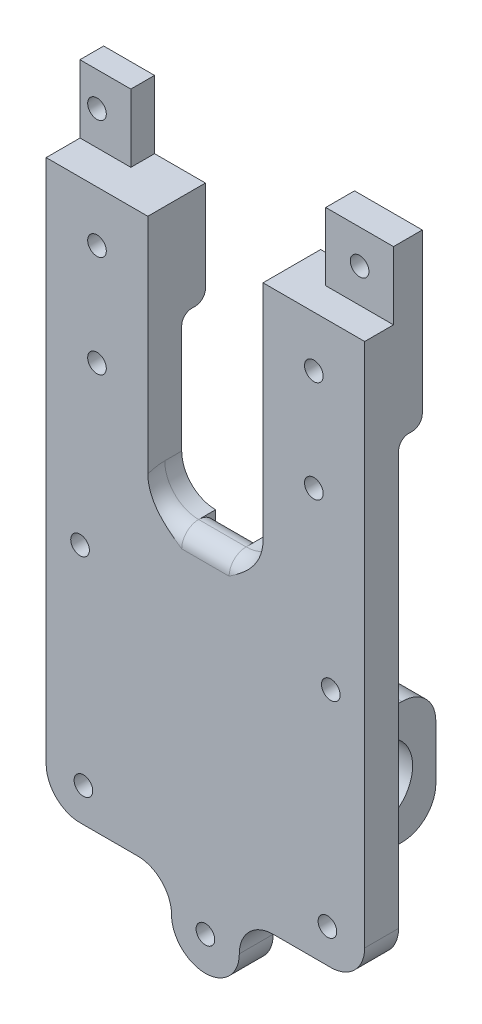
SolidWorks part; units mm, degrees
ref_plane "Front Plane" through (0, 0, 0) normal (0, 0, 1) x (1, 0, 0)
ref_plane "Top Plane" through (0, 0, 0) normal (0, 1, 0) x (1, 0, 0)
ref_plane "Right Plane" through (0, 0, 0) normal (1, 0, 0) x (0, 0, -1)
sketch "Sketch2" plane through (0, 0, -10) normal (0, 0, -1) x (-1, 0, 0)
  line L1 (-20, -75) -> (10, -75)
  line L2 (-20, -75) -> (-20, -205)
  line L3 (-20, -205) -> (10, -205)
  line L4 (10, -75) -> (10, -205)
  line L5 (44, -75) -> (74, -75)
  line L6 (44, -75) -> (44, -205)
  line L7 (44, -205) -> (74, -205)
  line L8 (74, -75) -> (74, -205)
  dimension "D1" = 130
  dimension "D2" = 130
  dimension "D3" = 30
  dimension "D4" = 30
extrude "Boss-Extrude1" add sketch "Sketch2" against normal up to surface (10 mm away)
sketch "Sketch3" plane through (0, 0, -10) normal (0, 0, -1) x (-1, 0, 0)
  line L0 (74, -205) -> (74, -75) construction
  line L1 (-20, -205) -> (74, -205)
  line L2 (-20, -205) -> (-20, -175)
  line L3 (-20, -175) -> (74, -175)
  line L4 (74, -205) -> (74, -175)
  dimension "D1" = 30
extrude "Boss-Extrude2" add sketch "Sketch3" against normal up to surface (10 mm away) up to face at (5, -140, 0)
fillet "Fillet1" radius 10 4 edges at (-74, -205, -5) (20, -205, -5) (-10, -175, -5) (-44, -175, -5)
sketch "Sketch4" plane through (0, 0, -10) normal (0, 0, -1) x (-1, 0, 0)
  line L0 (-20, -75) -> (-20, -155)
  line L1 (-20, -75) -> (-20, -195) construction
  line L2 (-20, -155) -> (74, -155)
  line L3 (74, -195) -> (74, -75) construction
  line L12 (-10, -205) -> (64, -205)
  line L13 (74, -195) -> (74, -75)
  line L14 (74, -75) -> (44, -75)
  line L15 (44, -75) -> (44, -165)
  line L16 (34, -175) -> (20, -175)
  line L17 (10, -165) -> (10, -75)
  line L18 (10, -75) -> (-20, -75)
  line L19 (-20, -75) -> (-20, -195)
  line L20 (-10, -205) -> (64, -205)
  line L21 (74, -195) -> (74, -75)
  line L22 (74, -75) -> (44, -75)
  line L23 (44, -75) -> (44, -165)
  line L24 (34, -175) -> (20, -175)
  line L25 (10, -165) -> (10, -75)
  line L26 (10, -75) -> (-20, -75)
  line L27 (-20, -75) -> (-20, -195)
  arc A4 (64, -205) -> (74, -195) centre (64, -195) ccw
  arc A5 (34, -175) -> (44, -165) centre (34, -165) ccw
  arc A6 (10, -165) -> (20, -175) centre (20, -165) ccw
  arc A7 (-20, -195) -> (-10, -205) centre (-10, -195) ccw
  arc A8 (64, -205) -> (74, -195) centre (64, -195) ccw
  arc A9 (34, -175) -> (44, -165) centre (34, -165) ccw
  arc A10 (10, -165) -> (20, -175) centre (20, -165) ccw
  arc A11 (-20, -195) -> (-10, -205) centre (-10, -195) ccw
  line M14 (-10, -205) -> (64, -205)
  arc M15 (64, -205) -> (74, -195) centre (64, -195) ccw
  line M16 (74, -195) -> (74, -75)
  line M18 (44, -75) -> (44, -165)
  arc M19 (44, -165) -> (34, -175) centre (34, -165) cw
  line M20 (34, -175) -> (20, -175)
  arc M21 (20, -175) -> (10, -165) centre (20, -165) cw
  line M22 (10, -165) -> (10, -75)
  line M24 (-20, -75) -> (-20, -195)
  arc M25 (-20, -195) -> (-10, -205) centre (-10, -195) ccw
  dimension "D1" = 80
  dimension "D2" = 0
extrude "Cut-Extrude1" cut sketch "Sketch4" against normal through all contours L2 M24 M25 M14 M15 M16 M18 M19 M20 M21 M22 region at (-27, -182.217, -10)
sketch "Sketch5" plane through (0, 0, -10) normal (0, 0, -1) x (-1, 0, 0)
  line L0 (74, -155) -> (74, -185)
  line L1 (-20, -155) -> (74, -155)
  line L2 (-20, -155) -> (-20, -185)
  line L3 (-20, -185) -> (74, -185)
  dimension "D1" = 30
extrude "Boss-Extrude3" add sketch "Sketch5" against normal up to surface (10 mm away) up to face at (5, -115, 0)
sketch "Sketch7" plane through (0, 0, -10) normal (0, 0, -1) x (-1, 0, 0)
  line L0 (10, -155) -> (-20, -155)
  line L2 (-20, -75) -> (-20, -185) construction
  line L4 (-5, -155) -> (-5, -175)
  line L5 (-10, -155) -> (-10, -175)
  line L6 (0, -155) -> (0, -175)
  line L7 (-10, -175) -> (0, -175)
  line L8 (-10, -155) -> (0, -155)
  line L9 (27, -155) -> (27, -148.1349)
  line L10 (44, -155) -> (10, -155) construction
  line L11 (64, -155) -> (54, -155)
  line L12 (64, -175) -> (54, -175)
  line L13 (54, -155) -> (54, -175)
  line L14 (64, -155) -> (64, -175)
  line L15 (59, -155) -> (59, -175)
  dimension "D3" = 20
  dimension "D1" = 5
  dimension "D2" = 5
extrude "Boss-Extrude4" add sketch "Sketch7" along normal blind 15 contours L5 L7 L4 L0 | L4 L7 L6 L0 | L15 L11 L13 L12 | L11 L15 L12 L14 region at (2.5, -165, -10) region at (7.5, -165, -10) region at (-61.5, -165, -10) region at (-56.5, -165, -10)
sketch "Sketch11" plane through (0, 0, -25) normal (0, 0, -1) x (-1, 0, 0)
  line L4 (54, -175) -> (64, -175)
  line L5 (64, -175) -> (64, -155)
  line L6 (64, -155) -> (54, -155)
  line L7 (54, -155) -> (54, -175)
  line L8 (54, -175) -> (64, -175)
  line L9 (64, -175) -> (64, -155)
  line L10 (64, -155) -> (54, -155)
  line L11 (54, -155) -> (54, -175)
  line L12 (-10, -155) -> (-10, -175)
  line L13 (-10, -175) -> (0, -175)
  line L14 (0, -175) -> (0, -155)
  line L15 (0, -155) -> (-10, -155)
  line L16 (-10, -155) -> (-10, -175)
  line L17 (-10, -175) -> (0, -175)
  line L18 (0, -175) -> (0, -155)
  line L19 (0, -155) -> (-10, -155)
  dimension "D1" = 0
  dimension "D2" = 0
extrude "Boss-Extrude5" add sketch "Sketch11" along normal blind 10
sketch "Sketch12" plane through (0, -175, 0) normal (0, -1, 0) x (1, 0, 0)
  line L4 (10, -10) -> (0, -10)
  line L5 (0, -10) -> (0, -35)
  line L6 (0, -35) -> (10, -35)
  line L7 (10, -35) -> (10, -10)
  line L8 (10, -10) -> (0, -10)
  line L9 (0, -10) -> (0, -35)
  line L10 (0, -35) -> (10, -35)
  line L11 (10, -35) -> (10, -10)
  line L12 (-54, -10) -> (-64, -10)
  line L13 (-64, -10) -> (-64, -35)
  line L14 (-64, -35) -> (-54, -35)
  line L15 (-54, -35) -> (-54, -10)
  line L16 (-54, -10) -> (-64, -10)
  line L17 (-64, -10) -> (-64, -35)
  line L18 (-64, -35) -> (-54, -35)
  line L19 (-54, -35) -> (-54, -10)
  dimension "D1" = 0
  dimension "D2" = 0
extrude "Boss-Extrude6" add sketch "Sketch12" along normal up to surface (10 mm away) up to face at (-27, -185, -5)
sketch "Sketch14" plane through (0, 0, 0) normal (-1, 0, 0) x (0, 0, 1)
  line L4 (-10, -185) -> (-10, -155)
  line L5 (-10, -155) -> (-35, -155)
  line L6 (-35, -155) -> (-35, -185)
  line L7 (-35, -185) -> (-10, -185)
  line L8 (-10, -185) -> (-10, -155)
  line L9 (-10, -155) -> (-35, -155)
  line L10 (-35, -155) -> (-35, -185)
  line L11 (-35, -185) -> (-10, -185)
  dimension "D1" = 0
extrude "Boss-Extrude7" add sketch "Sketch14" along normal blind 20
sketch "Sketch15" plane through (-54, 0, 0) normal (1, 0, 0) x (0, 0, -1)
  line L4 (10, -155) -> (10, -185)
  line L5 (10, -185) -> (35, -185)
  line L6 (35, -185) -> (35, -155)
  line L7 (35, -155) -> (10, -155)
  line L8 (10, -155) -> (10, -185)
  line L9 (10, -185) -> (35, -185)
  line L10 (35, -185) -> (35, -155)
  line L11 (35, -155) -> (10, -155)
  dimension "D1" = 0
extrude "Boss-Extrude8" add sketch "Sketch15" along normal blind 20
sketch "Sketch17" plane through (10, 0, 0) normal (1, 0, 0) x (0, 0, -1)
  line L4 (10, -155) -> (10, -185)
  line L5 (10, -185) -> (35, -185)
  line L6 (35, -185) -> (35, -155)
  line L7 (35, -155) -> (10, -155)
  line L8 (10, -155) -> (10, -185)
  line L9 (10, -185) -> (35, -185)
  line L10 (35, -185) -> (35, -155)
  line L11 (35, -155) -> (10, -155)
  dimension "D1" = 0
extrude "Cut-Extrude2" cut sketch "Sketch17" against normal blind 10
sketch "Sketch18" plane through (-64, 0, 0) normal (-1, 0, 0) x (0, 0, 1)
  line L4 (-10, -185) -> (-10, -155)
  line L5 (-10, -155) -> (-35, -155)
  line L6 (-35, -155) -> (-35, -185)
  line L7 (-35, -185) -> (-10, -185)
  line L8 (-10, -185) -> (-10, -155)
  line L9 (-10, -155) -> (-35, -155)
  line L10 (-35, -155) -> (-35, -185)
  line L11 (-35, -185) -> (-10, -185)
  dimension "D1" = 0
extrude "Cut-Extrude3" cut sketch "Sketch18" against normal blind 10
sketch "Sketch19" plane through (-34, 0, 0) normal (1, 0, 0) x (0, 0, -1)
  line L0 (35, -170) -> (10, -170)
  line L1 (35, -185) -> (35, -155) construction
  line L2 (10, -155) -> (10, -185) construction
  circle A0 centre (22.5, -170) radius 8
  dimension "D1" = 16
extrude "Cut-Extrude4" cut sketch "Sketch19" against normal through all both and the other way through all contours L0 A0 | L0 A0 region at (-34, -173.3953, -22.5) region at (-34, -166.6047, -22.5)
sketch "Sketch20" plane through (0, 0, 0) normal (1, 0, 0) x (0, 0, -1)
  circle A0 centre (22.5, -170) radius 11.15
  dimension "D1" = 22.3
extrude "Cut-Extrude5" cut sketch "Sketch20" against normal blind 10
sketch "Sketch21" plane through (-54, 0, 0) normal (-1, 0, 0) x (0, 0, 1)
  circle A0 centre (-22.5, -170) radius 11.15 construction
  circle A1 centre (-22.5, -170) radius 11.15
extrude "Cut-Extrude6" cut sketch "Sketch21" against normal blind 10
sketch "Sketch22" plane through (0, 0, -35) normal (0, 0, -1) x (-1, 0, 0)
  line L4 (34, -185) -> (54, -185)
  line L5 (54, -185) -> (54, -155)
  line L6 (54, -155) -> (34, -155)
  line L7 (34, -155) -> (34, -185)
  line L8 (34, -185) -> (54, -185)
  line L9 (54, -185) -> (54, -155)
  line L10 (54, -155) -> (34, -155)
  line L11 (34, -155) -> (34, -185)
  line L12 (20, -155) -> (0, -155)
  line L13 (0, -155) -> (0, -185)
  line L14 (0, -185) -> (20, -185)
  line L15 (20, -185) -> (20, -155)
  line L16 (20, -155) -> (0, -155)
  line L17 (0, -155) -> (0, -185)
  line L18 (0, -185) -> (20, -185)
  line L19 (20, -185) -> (20, -155)
  dimension "D1" = 0
  dimension "D2" = 0
extrude "Boss-Extrude9" add sketch "Sketch22" along normal blind 5
sketch "Sketch23" plane through (0, -185, 0) normal (0, -1, 0) x (1, 0, 0)
  line L12 (-74, -10) -> (-54, -10)
  line L13 (-54, -10) -> (-54, -40)
  line L14 (-54, -40) -> (-34, -40)
  line L15 (-34, -40) -> (-34, -10)
  line L16 (-34, -10) -> (-20, -10)
  line L17 (-20, -10) -> (-20, -40)
  line L18 (-20, -40) -> (0, -40)
  line L19 (0, -40) -> (0, -10)
  line L20 (0, -10) -> (20, -10)
  line L21 (20, -10) -> (20, 0)
  line L22 (20, 0) -> (-74, 0)
  line L23 (-74, 0) -> (-74, -10)
  line L24 (-74, -10) -> (-54, -10)
  line L25 (-54, -10) -> (-54, -40)
  line L26 (-54, -40) -> (-34, -40)
  line L27 (-34, -40) -> (-34, -10)
  line L28 (-34, -10) -> (-20, -10)
  line L29 (-20, -10) -> (-20, -40)
  line L30 (-20, -40) -> (0, -40)
  line L31 (0, -40) -> (0, -10)
  line L32 (0, -10) -> (20, -10)
  line L33 (20, -10) -> (20, 0)
  line L34 (20, 0) -> (-74, 0)
  line L35 (-74, 0) -> (-74, -10)
  dimension "D1" = 0
extrude "Boss-Extrude10" add sketch "Sketch23" along normal blind 5
sketch "Sketch24" plane through (0, -155, 0) normal (0, 1, 0) x (1, 0, 0)
  line L12 (-34, 10) -> (-34, 40)
  line L13 (-34, 40) -> (-54, 40)
  line L14 (-54, 40) -> (-54, 10)
  line L15 (-54, 10) -> (-44, 10)
  line L16 (-44, 10) -> (-44, 0)
  line L17 (-44, 0) -> (-10, 0)
  line L18 (-10, 0) -> (-10, 10)
  line L19 (-10, 10) -> (0, 10)
  line L20 (0, 10) -> (0, 40)
  line L21 (0, 40) -> (-20, 40)
  line L22 (-20, 40) -> (-20, 10)
  line L23 (-20, 10) -> (-34, 10)
  line L24 (-34, 10) -> (-34, 40)
  line L25 (-34, 40) -> (-54, 40)
  line L26 (-54, 40) -> (-54, 10)
  line L27 (-54, 10) -> (-44, 10)
  line L28 (-44, 10) -> (-44, 0)
  line L29 (-44, 0) -> (-10, 0)
  line L30 (-10, 0) -> (-10, 10)
  line L31 (-10, 10) -> (0, 10)
  line L32 (0, 10) -> (0, 40)
  line L33 (0, 40) -> (-20, 40)
  line L34 (-20, 40) -> (-20, 10)
  line L35 (-20, 10) -> (-34, 10)
  dimension "D1" = 0
extrude "Boss-Extrude11" add sketch "Sketch24" along normal blind 5
fillet "Fillet3" radius 10 6 edges at (-49, -150, -10) (-5, -150, -10) (-44, -190, -40) (-10, -190, -40) (-10, -150, -40) (-44, -150, -40)
fillet "Fillet4" radius 5 2 edges at (-27, -150, -10) (-27, -150, 0)
fillet "Fillet5" radius 10 6 edges at (-10, -151.4645, -1.4645) (-44, -151.4645, -1.4645) (-10, -150, -12.5) (-44, -150, -12.5) (-74, -190, -5) (20, -190, -5)
sketch "Sketch25" plane through (0, -190, 0) normal (0, -1, 0) x (1, 0, 0)
  line L1 (10, -10) -> (-64, -10)
  line L2 (10, -10) -> (10, 0)
  line L3 (10, 0) -> (-64, 0)
  line L4 (-64, -10) -> (-64, 0)
extrude "Boss-Extrude12" add sketch "Sketch25" along normal blind 20
fillet "Fillet6" radius 10 2 edges at (-64, -210, -5) (10, -210, -5)
sketch "Sketch26" plane through (0, 0, -10) normal (0, 0, -1) x (-1, 0, 0)
  line L0 (59, -75) -> (59, -105)
  line L1 (74, -75) -> (44, -75) construction
  line L2 (-5, -75) -> (-5, -105)
  line L3 (10, -75) -> (-20, -75) construction
  line L4 (-5, -105) -> (1.7665, -105)
  line L5 (59, -105) -> (52.1283, -105)
  line L6 (54, -140) -> (74, -140)
  line L7 (74, -180) -> (74, -75) construction
  line L8 (0, -140) -> (-20, -140)
  line L9 (-20, -75) -> (-20, -180) construction
  circle A0 centre (0, -200) radius 2.75
  circle A1 centre (54, -200) radius 2.75
  circle A2 centre (-5, -90) radius 2.75
  circle A3 centre (59, -90) radius 2.75
  circle A4 centre (-5, -120) radius 2.75
  circle A5 centre (59, -120) radius 2.75
  circle A6 centre (-10, -140) radius 2.75
  circle A7 centre (64, -140) radius 2.75
  dimension "D1" = 5.5
  dimension "D2" = 5.5
  dimension "D3" = 5.5
  dimension "D4" = 5.5
  dimension "D5" = 5.5
  dimension "D6" = 5.5
extrude "Cut-Extrude8" cut sketch "Sketch26" against normal through all both and the other way through all contours A4 | L2 A2 | L2 A2 | L8 A6 | L8 A6 | L0 A3 | L0 A3 | A5 | L6 A7 | L6 A7 | A1 | A0 region at (-60.1671, -90, -10) region at (-57.8329, -90, -10) region at (3.8329, -90, -10) region at (6.1671, -90, -10) region at (-64, -138.8329, -10) region at (-64, -141.1671, -10) region at (10, -141.1671, -10) region at (10, -138.8329, -10) region at (0, -200, -10) region at (-54, -200, -10) region at (5, -120, -10) region at (-59, -120, -10)
sketch "Sketch27" plane through (0, 0, -10) normal (0, 0, -1) x (-1, 0, 0)
  line L0 (27, -150) -> (27, -143.2701)
  line L1 (10, -75) -> (0, -75)
  line L2 (10, -75) -> (10, -105)
  line L3 (10, -105) -> (0, -105)
  line L4 (0, -75) -> (0, -105)
  line L5 (34, -150) -> (20, -150) construction
  line L6 (54, -75) -> (54, -105)
  line L7 (44, -105) -> (54, -105)
  line L8 (44, -75) -> (44, -105)
  line L9 (44, -75) -> (54, -75)
  dimension "D1" = 30
extrude "Boss-Extrude13" add sketch "Sketch27" along normal up to surface (7 mm away) contours L2 L1 L4 L3 | L6 L7 L8 L9
sketch "Sketch28" plane through (0, 0, -10) normal (0, 0, -1) x (-1, 0, 0)
  line L0 (-20, -75) -> (-20, -7.2161) construction
  line L1 (10, -105) -> (-20, -105)
  line L2 (10, -105) -> (10, -55)
  line L3 (10, -55) -> (-20, -55)
  line L4 (-20, -105) -> (-20, -55)
  line L5 (0, -75) -> (0, -55)
  line L6 (44, -105) -> (74.0263, -105)
  line L7 (44, -105) -> (44, -55)
  line L8 (44, -55) -> (74.0263, -55)
  line L9 (74.0263, -105) -> (74.0263, -55)
  line L10 (0, -75) -> (0, -15) construction
  line L11 (59.0132, -55) -> (59, -75)
  line L12 (74, -75) -> (54, -75) construction
  line L13 (59, -11.15) -> (59, -75) construction
  line L14 (59, -75) -> (54, -75)
  line L15 (54, -75) -> (54, -105)
  line L16 (0, -75) -> (0, -105)
  circle A0 centre (59, -90) radius 2.75 construction
  circle A1 centre (69, -65) radius 2.75 construction
  circle A2 centre (-10, -65) radius 2.75 construction
  circle A3 centre (-5, -90) radius 2.75 construction
  circle A4 centre (59, -90) radius 2.75
  circle A5 centre (69, -65) radius 2.75
  circle A6 centre (-10, -65) radius 2.75
  circle A7 centre (-5, -90) radius 2.75
  circle M14 centre (59, -90) radius 2.75
  circle M16 centre (-5, -90) radius 2.75
  line M17 (54, -75) -> (54, -105)
  line M31 (0, -105) -> (0, -75)
  line M32 (0, -75) -> (-20, -75)
  line M33 (-20, -75) -> (-20, -180)
  line M41 (74, -180) -> (74, -75)
  line M42 (74, -75) -> (54, -75)
  dimension "D1" = 50
  dimension "D2" = 50
extrude "Boss-Extrude14" add sketch "Sketch28" along normal up to surface (7 mm away) contours L6 M17 M41 M42 M14 | L8 L11 L6 L9 A5 M42 M41 | L5 L3 L4 A6 M32 | L1 M31 M32 M33 M16 region at (10.2061, -90, -10) region at (10, -74.7172, -10) region at (-64.2061, -90, -10) region at (-66.5, -74.4779, -10) up to face at (-5, -90, -17)
fillet "Fillet7" radius 3 4 edges at (-59.0132, -105, -17) (5, -105, -17) (5, -105, -10) (-59, -105, -10)
fillet "Fillet8" radius 5 2 edges at (-64, -190, -5) (10, -190, -5)
sketch "Sketch29" plane through (-44, 0, 0) normal (-1, 0, 0) x (0, 0, 1)
  circle A1 centre (-22.5, -170) radius 11.15
  circle A2 centre (-22.5, -170) radius 11.15
  dimension "D1" = 0
extrude "Cut-Extrude9" cut sketch "Sketch29" against normal blind 3
sketch "Sketch30" plane through (-10, 0, 0) normal (1, 0, 0) x (0, 0, -1)
  circle A1 centre (22.5, -170) radius 11.15
  circle A2 centre (22.5, -170) radius 11.15
  dimension "D1" = 0
extrude "Cut-Extrude10" cut sketch "Sketch30" against normal blind 3
sketch "Sketch31" plane through (-13, 0, 0) normal (1, 0, 0) x (0, 0, -1)
  circle A1 centre (22.5, -170) radius 11.15
  circle A2 centre (22.5, -170) radius 11.15
  dimension "D1" = 0
extrude "Cut-Extrude11" cut sketch "Sketch31" against normal blind 3
sketch "Sketch32" plane through (-41, 0, 0) normal (-1, 0, 0) x (0, 0, 1)
  circle A1 centre (-22.5, -170) radius 11.15
  circle A2 centre (-22.5, -170) radius 11.15
  dimension "D1" = 0
extrude "Cut-Extrude12" cut sketch "Sketch32" against normal blind 3
fillet "Fillet9" radius 5 2 edges at (-44, -190, -10) (-10, -190, -10)
sketch "Sketch33" plane through (0, 0, -10) normal (0, 0, -1) x (-1, 0, 0)
  line L0 (27, -210) -> (27, -240)
  line L1 (54, -210) -> (0, -210) construction
  line L2 (54, -210) -> (0, -210)
  line L4 (-10, -200) -> (64, -200)
  line L5 (-10, -200) -> (-10, -240)
  line L6 (-10, -240) -> (64, -240)
  line L7 (64, -200) -> (64, -240)
  arc A0 (-10, -200) -> (0, -210) centre (0, -200) ccw construction
  arc A1 (-10, -200) -> (0, -210) centre (0, -200) ccw
  arc A2 (54, -210) -> (64, -200) centre (54, -200) ccw construction
  arc A3 (54, -210) -> (64, -200) centre (54, -200) ccw
  dimension "D1" = 30
  dimension "D2" = 40
extrude "Boss-Extrude15" add sketch "Sketch33" against normal up to surface (10 mm away) contours L5 L6 L0 | L7 L0 L6 region at (-45.8085, -224.6731, -10) region at (-8.1915, -224.6731, -10) up to face at (7.25, -140, 0)
sketch "Sketch35" plane through (0, 0, -10) normal (0, 0, -1) x (-1, 0, 0)
  line L0 (27, -240) -> (27, -185)
  line L1 (-10, -240) -> (64, -240) construction
  line L2 (32, -240) -> (32, -185)
  line L3 (22, -240) -> (22, -185)
  line L4 (32, -212.5) -> (52, -212.5)
  line L5 (22, -212.5) -> (2, -212.5)
  line L6 (32, -227.5) -> (52, -227.5)
  line L7 (22, -197.5) -> (2, -197.5)
  line L8 (32, -197.5) -> (52, -197.5)
  line L9 (22, -227.5) -> (2, -227.5)
  line L10 (2, -197.5) -> (2, -227.5)
  line L11 (52, -197.5) -> (52, -227.5)
  line L12 (22, -197.5) -> (22, -227.5)
  line L13 (32, -227.5) -> (32, -197.5)
  circle M28 centre (54, -200) radius 2.75
  circle M29 centre (0, -200) radius 2.75
  dimension "D1" = 55
  dimension "D4" = 20
  dimension "D5" = 20
  dimension "D2" = 5
  dimension "D3" = 5
  dimension "D6" = 15
  dimension "D7" = 15
extrude "Boss-Extrude17" add sketch "Sketch35" along normal blind 30 contours L7 L10 L5 L3 M29 | L5 L10 L9 L3 | L11 L8 L2 L4 M28 | L11 L4 L2 L6 | L10 M29 | L11 L6 L13 L8 region at (-42, -220, -10) region at (-41.9367, -205.0326, -10) region at (-12, -220, -10) region at (-12.0633, -205.0326, -10) region at (-2.3038, -200, -10)
sketch "Sketch36" plane through (0, 0, 0) normal (0, 0, 1) x (1, 0, 0)
  circle A0 centre (-54, -200) radius 2.75
  circle A1 centre (0, -200) radius 2.75
extrude "Boss-Extrude18" add sketch "Sketch36" against normal up to surface (10 mm away) up to face at (-46.125, -208.3333, -10)
sketch "Sketch37" plane through (-52, 0, 0) normal (-1, 0, 0) x (0, 0, 1)
  line L0 (-40, -212.5) -> (-10, -212.5)
  line L1 (-40, -197.5) -> (-40, -227.5) construction
  line L2 (-10, -240) -> (-10, -194.1421) construction
  circle A0 centre (-25, -212.5) radius 8
  dimension "D1" = 16
extrude "Cut-Extrude14" cut sketch "Sketch37" against normal through all both and the other way through all contours L0 A0 | L0 A0 region at (-52, -209.1047, -25) region at (-52, -215.8953, -25)
sketch "Sketch41" plane through (-52, 0, 0) normal (-1, 0, 0) x (0, 0, 1)
  circle A0 centre (-25, -212.5) radius 11.15
  dimension "D1" = 22.3
extrude "Cut-Extrude15" cut sketch "Sketch41" against normal blind 15
sketch "Sketch42" plane through (-2, 0, 0) normal (1, 0, 0) x (0, 0, -1)
  circle A0 centre (25, -212.5) radius 11.15 construction
  circle A1 centre (25, -212.5) radius 11.15
extrude "Cut-Extrude16" cut sketch "Sketch42" against normal blind 15
sketch "Sketch43" plane through (0, 0, -40) normal (0, 0, -1) x (-1, 0, 0)
  line L1 (0, -140) -> (54, -140)
  line L2 (0, -140) -> (0, -195)
  line L3 (0, -195) -> (54, -195)
  line L4 (54, -140) -> (54, -195)
extrude "Cut-Extrude17" cut sketch "Sketch43" against normal up to surface (30 mm away) up to face at (-42, -212.5, -10)
sketch "Sketch44" plane through (0, -227.5, 0) normal (0, -1, 0) x (1, 0, 0)
  line L4 (-2, -10) -> (-22, -10)
  line L5 (-22, -10) -> (-22, -40)
  line L6 (-22, -40) -> (-2, -40)
  line L7 (-2, -40) -> (-2, -10)
  line L8 (-2, -10) -> (-22, -10)
  line L9 (-22, -10) -> (-22, -40)
  line L10 (-22, -40) -> (-2, -40)
  line L11 (-2, -40) -> (-2, -10)
  line L12 (-32, -10) -> (-52, -10)
  line L13 (-52, -10) -> (-52, -40)
  line L14 (-52, -40) -> (-32, -40)
  line L15 (-32, -40) -> (-32, -10)
  line L16 (-32, -10) -> (-52, -10)
  line L17 (-52, -10) -> (-52, -40)
  line L18 (-52, -40) -> (-32, -40)
  line L19 (-32, -40) -> (-32, -10)
  dimension "D1" = 0
  dimension "D2" = 0
extrude "Boss-Extrude19" add sketch "Sketch44" along normal blind 3
sketch "Sketch45" plane through (0, -197.5, 0) normal (0, 1, 0) x (1, 0, 0)
  line L4 (-22, 10) -> (-2, 10)
  line L5 (-2, 10) -> (-2, 40)
  line L6 (-2, 40) -> (-22, 40)
  line L7 (-22, 40) -> (-22, 10)
  line L8 (-22, 10) -> (-2, 10)
  line L9 (-2, 10) -> (-2, 40)
  line L10 (-2, 40) -> (-22, 40)
  line L11 (-22, 40) -> (-22, 10)
  line L12 (-52, 10) -> (-32, 10)
  line L13 (-32, 10) -> (-32, 40)
  line L14 (-32, 40) -> (-52, 40)
  line L15 (-52, 40) -> (-52, 10)
  line L16 (-52, 10) -> (-32, 10)
  line L17 (-32, 10) -> (-32, 40)
  line L18 (-32, 40) -> (-52, 40)
  line L19 (-52, 40) -> (-52, 10)
  dimension "D1" = 0
  dimension "D2" = 0
extrude "Boss-Extrude20" add sketch "Sketch45" along normal blind 3
sketch "Sketch46" plane through (0, 0, -40) normal (0, 0, -1) x (-1, 0, 0)
  line L4 (52, -230.5) -> (52, -194.5)
  line L5 (52, -194.5) -> (32, -194.5)
  line L6 (32, -194.5) -> (32, -230.5)
  line L7 (32, -230.5) -> (52, -230.5)
  line L8 (52, -230.5) -> (52, -194.5)
  line L9 (52, -194.5) -> (32, -194.5)
  line L10 (32, -194.5) -> (32, -230.5)
  line L11 (32, -230.5) -> (52, -230.5)
  line L12 (22, -230.5) -> (22, -194.5)
  line L13 (22, -194.5) -> (2, -194.5)
  line L14 (2, -194.5) -> (2, -230.5)
  line L15 (2, -230.5) -> (22, -230.5)
  line L16 (22, -230.5) -> (22, -194.5)
  line L17 (22, -194.5) -> (2, -194.5)
  line L18 (2, -194.5) -> (2, -230.5)
  line L19 (2, -230.5) -> (22, -230.5)
  dimension "D1" = 0
  dimension "D2" = 0
extrude "Boss-Extrude21" add sketch "Sketch46" along normal blind 3
fillet "Fillet10" radius 10 8 edges at (-42, -194.5, -10) (-12, -194.5, -10) (-42, -230.5, -10) (-12, -230.5, -10) (-12, -230.5, -43) (-42, -230.5, -43) (-42, -194.5, -43) (-12, -194.5, -43)
sketch "Sketch48" plane through (0, 0, -10) normal (0, 0, -1) x (-1, 0, 0)
  line L0 (27, -240) -> (27, -252.4763)
  line L1 (22, -240) -> (32, -240) construction
  line L2 (22, -240) -> (22, -252.4763)
  line L3 (32, -240) -> (32, -252.4763)
  line L4 (74, -180) -> (74, -240)
  line L5 (74, -240) -> (64, -240)
  line L6 (64, -240) -> (64, -180)
  line L7 (64, -180) -> (74, -180)
  line L8 (-20, -180) -> (-20, -240)
  line L9 (-20, -240) -> (-10, -240)
  line L10 (-10, -240) -> (-10, -180)
  line L11 (-10, -180) -> (-20, -180)
  line M6 (64, -240) -> (64, -194.1421)
  arc M7 (64, -194.1421) -> (67.3333, -189.4281) centre (69, -194.1421) cw
  arc M8 (67.3333, -189.4281) -> (74, -180) centre (64, -180) ccw
  arc M20 (-20, -180) -> (-13.3333, -189.4281) centre (-10, -180) ccw
  arc M21 (-13.3333, -189.4281) -> (-10, -194.1421) centre (-15, -194.1421) cw
  line M22 (-10, -194.1421) -> (-10, -240)
  dimension "D1" = 5
  dimension "D2" = 5
extrude "Boss-Extrude22" add sketch "Sketch48" against normal up to surface (10 mm away) contours L8 L9 M22 M21 M20 | L5 L4 M8 M7 M6 region at (-69.1389, -214.0112, -10) region at (15.1389, -214.0112, -10) up to face at (7.25, -140, 0)
sketch "Sketch49" plane through (0, 0, -10) normal (0, 0, -1) x (-1, 0, 0)
  line L0 (63, -240) -> (63, -230)
  line L1 (52, -240) -> (74, -240) construction
  line L2 (27, -240) -> (27, -260)
  line L3 (22, -240) -> (32, -240) construction
  line L4 (17, -240) -> (17, -260)
  line L5 (37, -240) -> (37, -260)
  circle A0 centre (63, -230) radius 2.75
  circle A1 centre (-9, -230) radius 2.75
  dimension "D2" = 5.5
  dimension "D1" = 10
  dimension "D5" = 20
  dimension "D3" = 10
  dimension "D4" = 10
extrude "Cut-Extrude18" cut sketch "Sketch49" against normal through all both and the other way through all contours A0 | A1 region at (-64.8895, -231.8895, -10) region at (9, -230, -10)
sketch "Sketch50" plane through (0, 0, -10) normal (0, 0, -1) x (-1, 0, 0)
  line L0 (27, -240) -> (27, -260)
  line L1 (22, -240) -> (32, -240) construction
  line L2 (17, -240) -> (17, -260)
  line L3 (37, -240) -> (37, -260)
  line L4 (37, -260) -> (17, -260)
  line L5 (17, -240) -> (37, -240)
  circle A0 centre (27, -250) radius 2.75
  line M19 (22, -240) -> (32, -240)
  dimension "D4" = 5.5
  dimension "D1" = 20
  dimension "D2" = 10
  dimension "D3" = 10
extrude "Boss-Extrude23" add sketch "Sketch50" against normal up to surface (10 mm away) contours A0 L0 L5 L2 L4 M19 | A0 L0 L4 L3 L5 M19 region at (-32.242, -250, -10) region at (-21.758, -250, -10) up to face at (2.25, -90, 0)
fillet "Fillet11" radius 10 6 edges at (-74, -240, -5) (-37, -240, -5) (-37, -260, -5) (-17, -260, -5) (-17, -240, -5) (20, -240, -5)
sketch "Sketch51" plane through (0, 0, -10) normal (0, 0, -1) x (-1, 0, 0)
  circle A0 centre (-10, -140) radius 2.75 construction
  circle A1 centre (64, -140) radius 2.75 construction
  circle A2 centre (-10, -140) radius 2.75
  circle A3 centre (64, -140) radius 2.75
extrude "Boss-Extrude24" add sketch "Sketch51" against normal up to surface (10 mm away) up to face at (2.25, -90, 0)
sketch "Sketch52" plane through (0, 0, -10) normal (0, 0, -1) x (-1, 0, 0)
  line L0 (-20, -169) -> (-10, -169)
  line L1 (-20, -108) -> (-20, -230) construction
  line L2 (27, -150) -> (27, -144.6344)
  line L3 (34, -150) -> (20, -150) construction
  circle A0 centre (-10, -169) radius 2.75
  circle A1 centre (64, -169) radius 2.75
  dimension "D2" = 5.5
  dimension "D1" = 10
extrude "Cut-Extrude19" cut sketch "Sketch52" against normal through all contours A0 | A1 region at (10, -171.6722, -10) region at (-64, -169, -10)
sketch "Sketch53" plane through (0, 0, -10) normal (0, 0, 1) x (1, 0, 0)
  line L4 (0, -75) -> (20, -75)
  line L5 (20, -75) -> (20, -55)
  line L6 (20, -55) -> (0, -55)
  line L7 (0, -55) -> (0, -75)
  line L8 (0, -75) -> (20, -75)
  line L9 (20, -75) -> (20, -55)
  line L10 (20, -55) -> (0, -55)
  line L11 (0, -55) -> (0, -75)
  circle A0 centre (10, -65) radius 2.75 construction
  circle A1 centre (10, -65) radius 2.75
  dimension "D1" = 0
extrude "Boss-Extrude25" add sketch "Sketch53" along normal up to surface (1.5 mm away)
